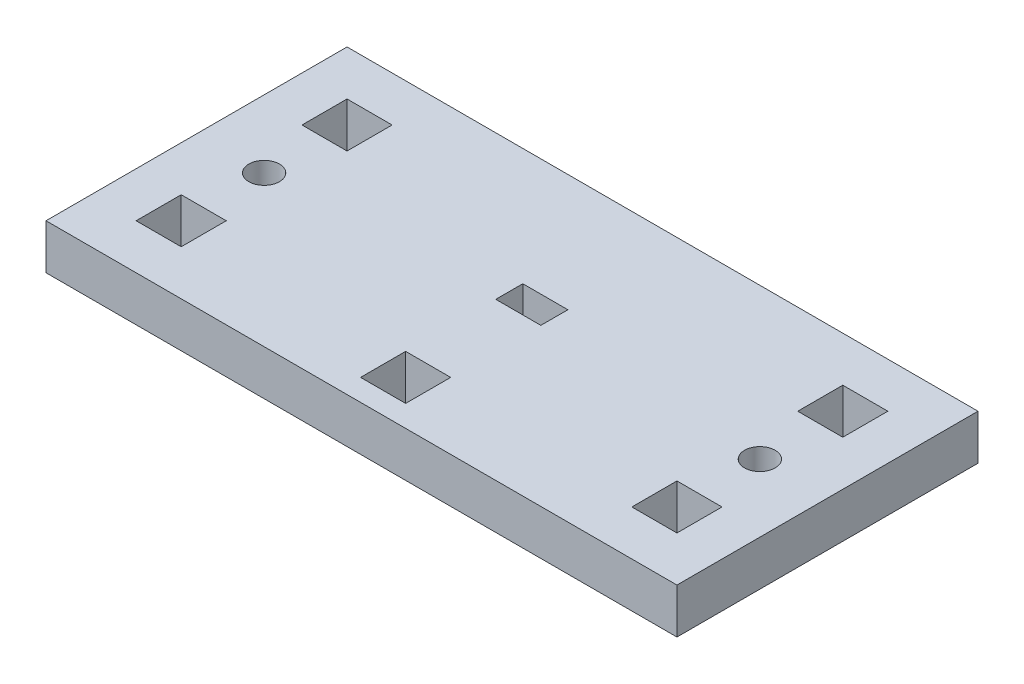
SolidWorks part; units mm, degrees
ref_plane "Front Plane" through (0, 0, 0) normal (0, 0, 1) x (1, 0, 0)
ref_plane "Top Plane" through (0, 0, 0) normal (0, 1, 0) x (1, 0, 0)
ref_plane "Right Plane" through (0, 0, 0) normal (1, 0, 0) x (0, 0, -1)
sketch "Sketch1" plane through (0, 0, 0) normal (0, 1, 0) x (1, 0, 0)
  line L0 (-44.45, 0) -> (44.45, 0) construction
  line L1 (-44.45, -21.209) -> (44.45, -21.209)
  line L2 (-44.45, -21.209) -> (-44.45, 21.209)
  line L3 (-44.45, 21.209) -> (44.45, 21.209)
  line L4 (44.45, -21.209) -> (44.45, 21.209)
  line L5 (-44.45, -21.209) -> (44.45, 21.209) construction
  line L6 (-44.45, 21.209) -> (44.45, -21.209) construction
  line L7 (0, 21.209) -> (0, -21.209) construction
  line L10 (-3.175, -11.811) -> (3.175, -11.811)
  line L11 (-3.175, -11.811) -> (-3.175, -18.161)
  line L12 (-3.175, -18.161) -> (3.175, -18.161)
  line L13 (3.175, -11.811) -> (3.175, -18.161)
  line L14 (-3.175, -11.811) -> (3.175, -18.161) construction
  line L15 (-3.175, -18.161) -> (3.175, -11.811) construction
  line L16 (-3.175, 0.889) -> (3.175, 0.889)
  line L17 (-3.175, 0.889) -> (-3.175, 4.699)
  line L18 (-3.175, 4.699) -> (3.175, 4.699)
  line L19 (3.175, 0.889) -> (3.175, 4.699)
  line L20 (-3.175, 0.889) -> (3.175, 4.699) construction
  line L21 (-3.175, 4.699) -> (3.175, 0.889) construction
  point P0 (0, 0)
  point P12 (0, -14.986)
  point P17 (0, 2.794)
  line B0 (31.75, 8.509) -> (38.1, 8.509)
  line B1 (31.75, 8.509) -> (31.75, 14.859)
  line B2 (31.75, 14.859) -> (38.1, 14.859)
  line B3 (38.1, 8.509) -> (38.1, 14.859)
  line B4 (38.1, -8.509) -> (38.1, -14.859)
  line B5 (31.75, -14.859) -> (38.1, -14.859)
  line B6 (31.75, -8.509) -> (31.75, -14.859)
  line B7 (31.75, -8.509) -> (38.1, -8.509)
  circle B8 centre (34.925, 0) radius 2.159
  line B9 (-31.75, 8.509) -> (-38.1, 8.509)
  line B10 (-31.75, 8.509) -> (-31.75, 14.859)
  line B11 (-31.75, 14.859) -> (-38.1, 14.859)
  line B12 (-38.1, 8.509) -> (-38.1, 14.859)
  line B13 (-38.1, -8.509) -> (-38.1, -14.859)
  line B14 (-31.75, -14.859) -> (-38.1, -14.859)
  line B15 (-31.75, -8.509) -> (-31.75, -14.859)
  line B16 (-31.75, -8.509) -> (-38.1, -8.509)
  circle B17 centre (-34.925, 0) radius 2.159
  dimension "D1" = 6.35
  dimension "D2" = 6.35
  dimension "D3" = 63.5
  dimension "D4" = 3.048
  dimension "D5" = 6.35
  dimension "D6" = 12.7
  dimension "D7" = 3.81
sketch_block_instance "Female T-Slot Assembly-1"
sketch_block "Female T-Slot Assembly" parameters "D4"=4.318, "D1"=6.35, "D2"=6.35, "D3"=6.35
sketch_block_instance "Female T-Slot Assembly-3"
extrude "Boss-Extrude1" add sketch "Sketch1" along normal blind 6.35
